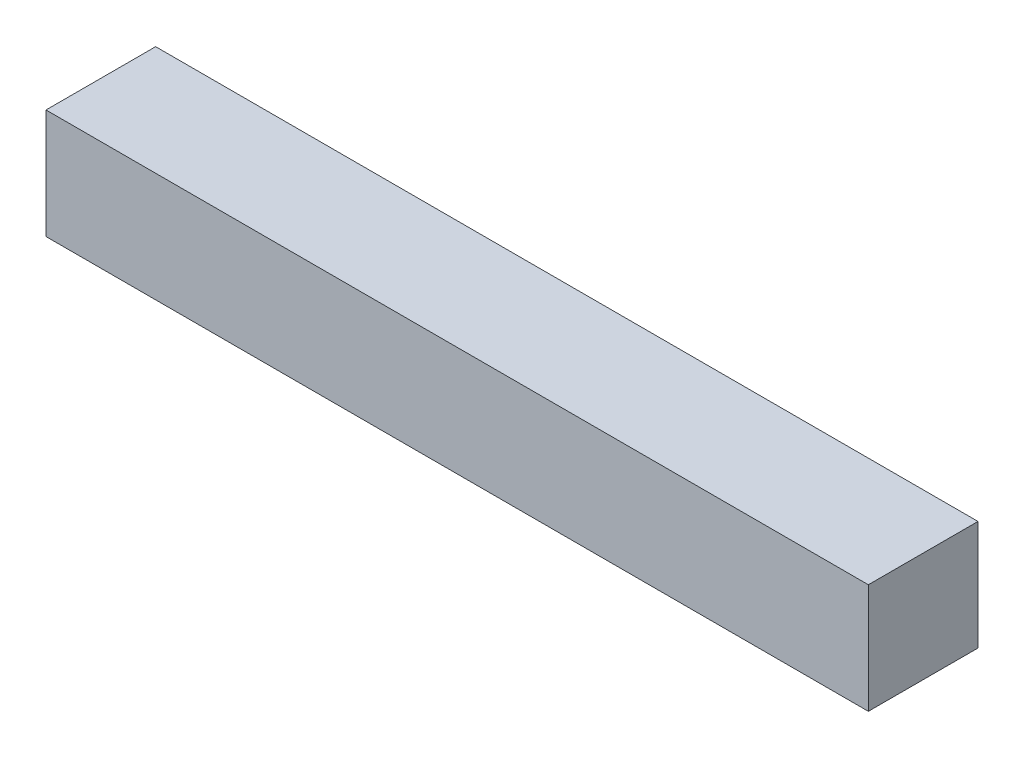
SolidWorks part; units mm, degrees
ref_plane "Front Plane" through (0, 0, 0) normal (0, 0, 1) x (1, 0, 0)
ref_plane "Top Plane" through (0, 0, 0) normal (0, 1, 0) x (1, 0, 0)
ref_plane "Right Plane" through (0, 0, 0) normal (1, 0, 0) x (0, 0, -1)
sketch "Sketch1" plane through (0, 0, 0) normal (1, 0, 0) x (0, 0, -1)
  line L1 (-10, -10) -> (10, -10)
  line L2 (-10, -10) -> (-10, 10)
  line L3 (-10, 10) -> (10, 10)
  line L4 (10, -10) -> (10, 10)
  line L5 (-10, -10) -> (10, 10) construction
  line L6 (-10, 10) -> (10, -10) construction
  point P0 (0, 0)
  dimension "D1" = 20
  dimension "D2" = 20
extrude "Boss-Extrude1" add sketch "Sketch1" along normal blind 75 and the other way blind 75
